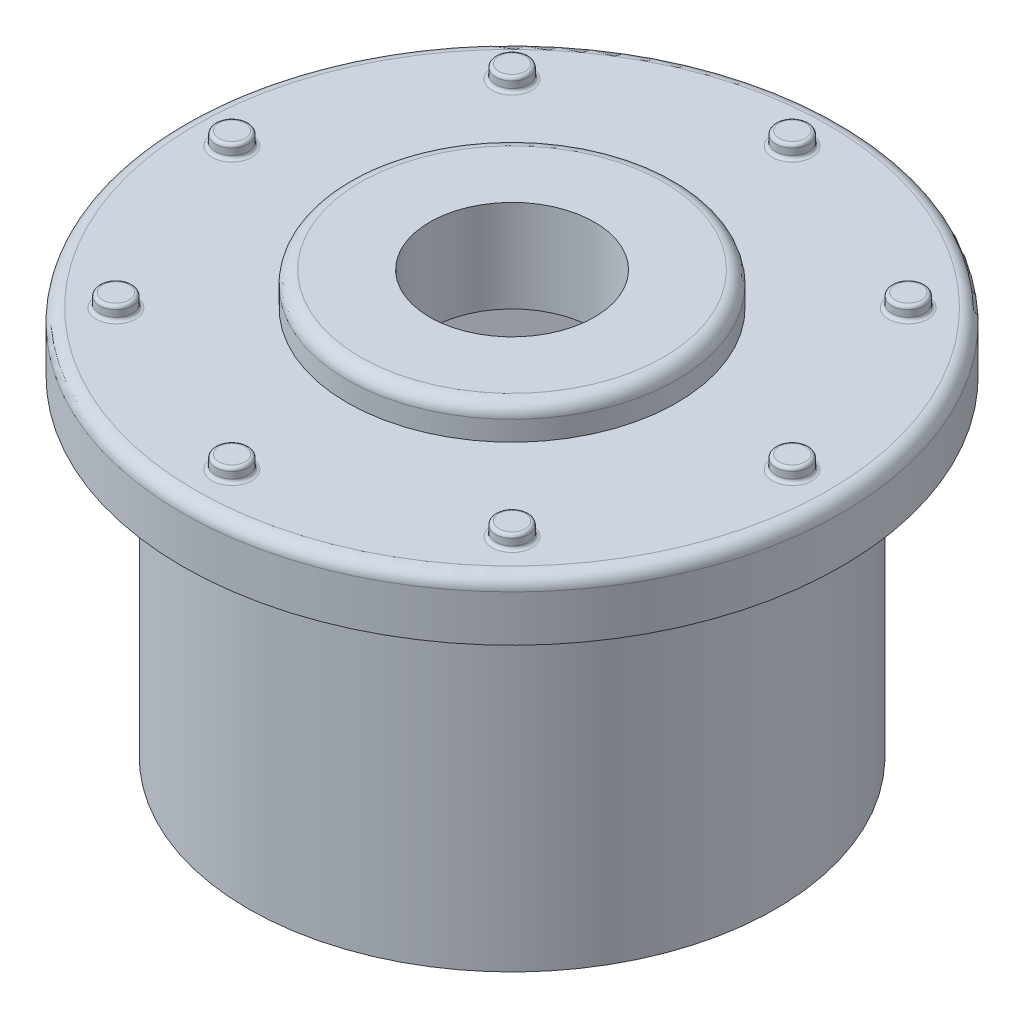
SolidWorks part; units mm, degrees
material "6061-T6 (SS)"
ref_plane "Front Plane" through (0, 0, 0) normal (0, 0, 1) x (1, 0, 0)
ref_plane "Top Plane" through (0, 0, 0) normal (0, 1, 0) x (1, 0, 0)
ref_plane "Right Plane" through (0, 0, 0) normal (1, 0, 0) x (0, 0, -1)
sketch "Sketch2" plane through (0, 0, 0) normal (0, 1, 0) x (1, 0, 0)
  circle A0 centre (0, 0) radius 5
  dimension "D1" = 10
extrude "Boss-Extrude1" add sketch "Sketch2" along normal blind 0.9 separate body
sketch "Sketch13" plane through (0, 0.9, 0) normal (0, 1, 0) x (1, 0, 0)
  line L0 (-5, 0) -> (0, 0) construction
  circle A0 centre (-4.25, 0) radius 0.25
  circle A1 centre (0, 0) radius 5 construction
  dimension "D1" = 0.5
  dimension "D2" = 0.75
extrude "Boss-Extrude4" add sketch "Sketch13" along normal blind 0.2
fillet "Fillet3" radius 0.05 2 edges at (-4.25, 0.9, 0.25) (-4.25, 1.1, 0.25)
pattern_circular "CirPattern3" count 8 over 360 about axis through (0, 0.9, 0) along (0, 1, 0) of "Boss-Extrude4", "Fillet3"
sketch "Sketch36" plane through (0, 0, 0) normal (0, 1, 0) x (1, 0, 0)
  circle A0 centre (0, 0) radius 4
  dimension "D1" = 8
extrude "Boss-Extrude5" add sketch "Sketch36" against normal blind 5
sketch "Sketch37" plane through (0, 0, 0) normal (0, 1, 0) x (1, 0, 0)
  line L7 (0, 3) -> (-2.5981, 1.5)
  line L8 (-2.5981, 1.5) -> (-2.5981, -1.5)
  line L9 (-2.5981, -1.5) -> (0, -3)
  line L10 (0, -3) -> (2.5981, -1.5)
  line L11 (2.5981, -1.5) -> (2.5981, 1.5)
  line L12 (2.5981, 1.5) -> (0, 3)
  circle A0 centre (0, 0) radius 3
  dimension "D1" = 6
extrude "Cut-Extrude5" cut sketch "Sketch37" against normal through all contours A0
extrude "Boss-Extrude7" add sketch "Sketch37<4>" against normal offset from surface (4.5 mm away) 0.5 separate body contours L7 A0 | L12 A0 | L11 A0 | L10 A0 | L9 A0 | L8 A0 region at (1.3799, 0, -2.3901) region at (-1.3799, 0, -2.3901) region at (-2.7598, 0, 0) region at (2.7598, 0, 0) region at (-1.3799, 0, 2.3901) region at (1.3799, 0, 2.3901) up to face at (0, -5, 3)
sketch "Sketch37<4>" plane through (0, 0, 0) normal (0, 1, 0) x (1, 0, 0) same geometry as "Sketch37"
sketch "Sketch39" plane through (0, 0.9, 0) normal (0, 1, 0) x (1, 0, 0)
  circle A0 centre (0, 0) radius 2.5
  dimension "D1" = 5
extrude "Boss-Extrude8" add sketch "Sketch39" along normal blind 0.5
sketch "Sketch40" plane through (0, 1.4, 0) normal (0, 1, 0) x (1, 0, 0)
  circle A0 centre (0, 0) radius 1.25
  dimension "D1" = 2.5
extrude "Cut-Extrude6" cut sketch "Sketch40" against normal through all
fillet "Fillet4" radius 0.2 2 edges at (0, 1.4, 2.5) (0, 0.9, 5)
ref_axis "Axis1" through (0, 0, 0) along (0, 1, 0)
